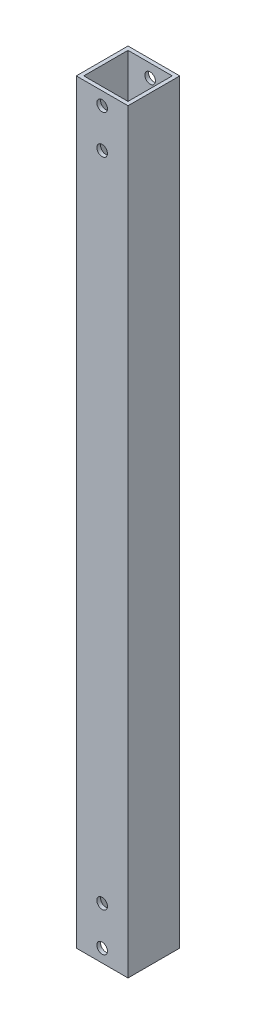
SolidWorks part; units mm, degrees
ref_plane "Front Plane" through (0, 0, 0) normal (0, 0, 1) x (1, 0, 0)
ref_plane "Top Plane" through (0, 0, 0) normal (0, 1, 0) x (1, 0, 0)
ref_plane "Right Plane" through (0, 0, 0) normal (1, 0, 0) x (0, 0, -1)
sketch "Sketch1" plane through (0, 0, 0) normal (0, 1, 0) x (1, 0, 0)
  line L0 (1.45, 18.55) -> (18.55, 18.55)
  line L1 (0, 0) -> (20, 0)
  line L2 (0, 0) -> (0, 20)
  line L3 (0, 20) -> (20, 20)
  line L4 (20, 0) -> (20, 20)
  line L5 (18.55, 1.45) -> (18.55, 18.55)
  line L6 (1.45, 1.45) -> (18.55, 1.45)
  line L7 (1.45, 1.45) -> (1.45, 18.55)
  dimension "D1" = 20
  dimension "D2" = 1.45
extrude "Boss-Extrude1" add sketch "Sketch1" along normal blind 292
sketch "Sketch2" plane through (0, 0, -20) normal (0, 0, -1) x (-1, 0, 0)
  line L0 (-20, 292) -> (0, 292) construction
  line L1 (-20, 292) -> (-20, 0) construction
  line L2 (-20, 0) -> (0, 0) construction
  circle A0 centre (-10, 287) radius 2.05
  circle A1 centre (-10, 272) radius 2.05
  circle A2 centre (-10, 20) radius 2.05
  circle A3 centre (-10, 5) radius 2.05
  dimension "D1" = 15
  dimension "D2" = 4.1
  dimension "D3" = 5
  dimension "D4" = 10
  dimension "D5" = 15
  dimension "D6" = 5
extrude "Cut-Extrude1" cut sketch "Sketch2" against normal through all
